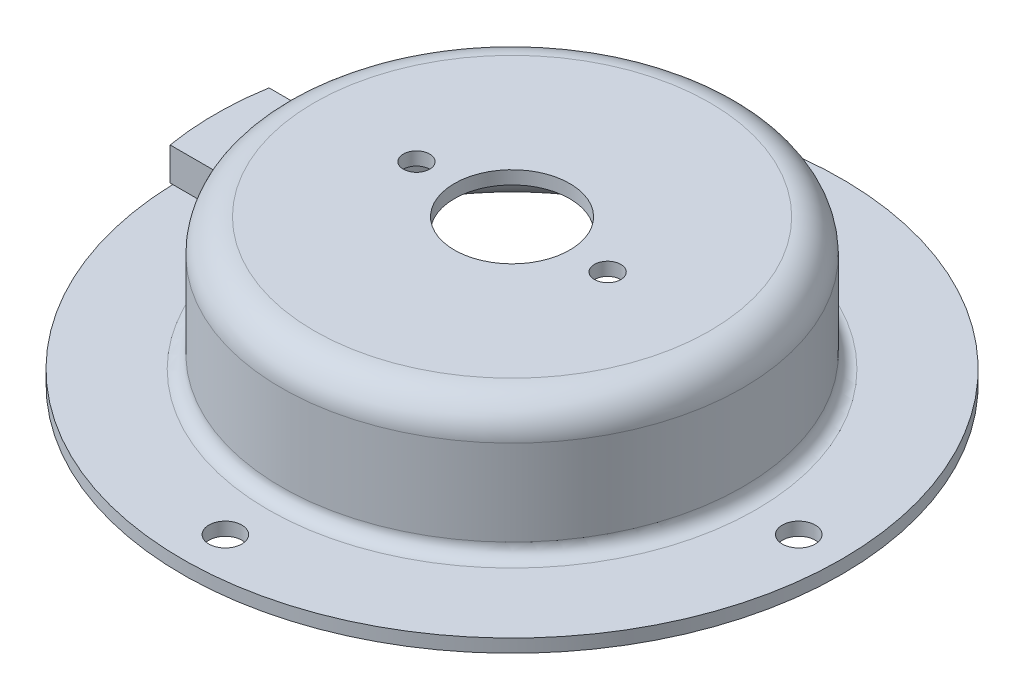
SolidWorks part; units mm, degrees
note: The reader was unsure of these and kept them because the rebuilt part matched: shared geometry of "Sketch3<2>".
ref_plane "Front Plane" through (0, 0, 0) normal (0, 0, 1) x (1, 0, 0)
ref_plane "Top Plane" through (0, 0, 0) normal (0, 1, 0) x (1, 0, 0)
ref_plane "Right Plane" through (0, 0, 0) normal (1, 0, 0) x (0, 0, -1)
sketch "Sketch1" plane through (0, 0, 0) normal (0, 0, 1) x (1, 0, 0)
  line L0 (0, -881.361) -> (0, 43186.6897) construction
  line L1 (0, 20) -> (30, 20)
  line L2 (35, 15) -> (35, 2)
  line L3 (37, 0) -> (50, 0)
  arc A0 (37, 0) -> (35, 2) centre (37, 2) cw
  arc A1 (35, 15) -> (30, 20) centre (30, 15) ccw
  point P9 (35, 0)
  point P12 (35, 20)
  point P13 (56.8717, 0)
  point P14 (0, 0)
  point P15 (0, 0)
  dimension "D4" = 2
  dimension "D5" = 5
  dimension "D1" = 35
  dimension "D2" = 20
  dimension "D3" = 15
revolve "Revolve-Thin1" add sketch "Sketch1" angle 360 about L0
sketch "Sketch2" plane through (0, 20, 0) normal (0, 1, 0) x (1, 0, 0)
  circle A0 centre (0, 0) radius 14.5 construction
  circle A1 centre (14.5, 0) radius 2
  circle A2 centre (-14.5, 0) radius 2
  circle A3 centre (0, 0) radius 8.75
  dimension "D1" = 29
  dimension "D2" = 4
  dimension "D3" = 17.5
extrude "Cut-Extrude1" cut sketch "Sketch2" against normal up to next
sketch "Sketch3" plane through (0, 0, 0) normal (1, 0, 0) x (0, 0, -1)
  line L0 (-35, 15) -> (-35, 2) construction
  line L1 (-7.5, 11) -> (7.5, 11)
  line L2 (-7.5, 11) -> (-7.5, 6)
  line L3 (-7.5, 6) -> (7.5, 6)
  line L4 (7.5, 11) -> (7.5, 6)
  line L5 (-7.5, 11) -> (7.5, 6) construction
  line L6 (-7.5, 6) -> (7.5, 11) construction
  line L7 (-1035, 8.5) -> (48965, 8.5) construction
  point P0 (0, 8.5)
  point P9 (0, 0)
  point P11 (-35, 8.5)
  dimension "D1" = 15
  dimension "D2" = 5
extrude "Cut-Extrude2" cut sketch "Sketch3" against normal up to next
extrude "Extrude-Thin1" add sketch "Sketch3<2>" against normal offset from surface (44.5281 mm away) 10 thin
sketch "Sketch3<2>" plane through (0, 0, 0) normal (1, 0, 0) x (0, 0, -1) same geometry as "Sketch3"
sketch "Sketch4" plane through (0, 6, 0) normal (0, -1, 0) x (1, 0, 0)
  line L3 (-44.3706, -7.5) -> (0, -7.5)
  line L4 (0, -7.5) -> (0, 7.5)
  line L5 (0, 7.5) -> (-44.3706, 7.5)
  line L6 (-32.1364, -7.5) -> (0, -7.5)
  line L7 (0, -7.5) -> (0, 7.5)
  line L8 (0, 7.5) -> (-32.1364, 7.5)
  arc A0 (-32.1364, 7.5) -> (-32.1364, -7.5) centre (0, 0) ccw
  arc A2 (-44.3706, 7.5) -> (-44.3706, -7.5) centre (0, 0) ccw
  dimension "D1" = 66
  dimension "D2" = 0
extrude "Cut-Extrude3" cut sketch "Sketch4" against normal up to next
sketch "Sketch5" plane through (0, 0, 0) normal (0, 1, 0) x (1, 0, 0)
  line L0 (0, 0) -> (0, 43.5) construction
  circle A1 centre (0, 43.5) radius 2.5
  circle A2 centre (43.5, 0) radius 2.5
  circle A3 centre (0, -43.5) radius 2.5
  circle A4 centre (-43.5, 0) radius 2.5
  circle A5 centre (0, 0) radius 37 construction
  dimension "D1" = 43.5
  dimension "D2" = 5
  dimension "D4" = 43.5
  dimension "D5" = 43.5
  dimension "D3" = 4
extrude "Cut-Extrude4" cut sketch "Sketch5" against normal through all
